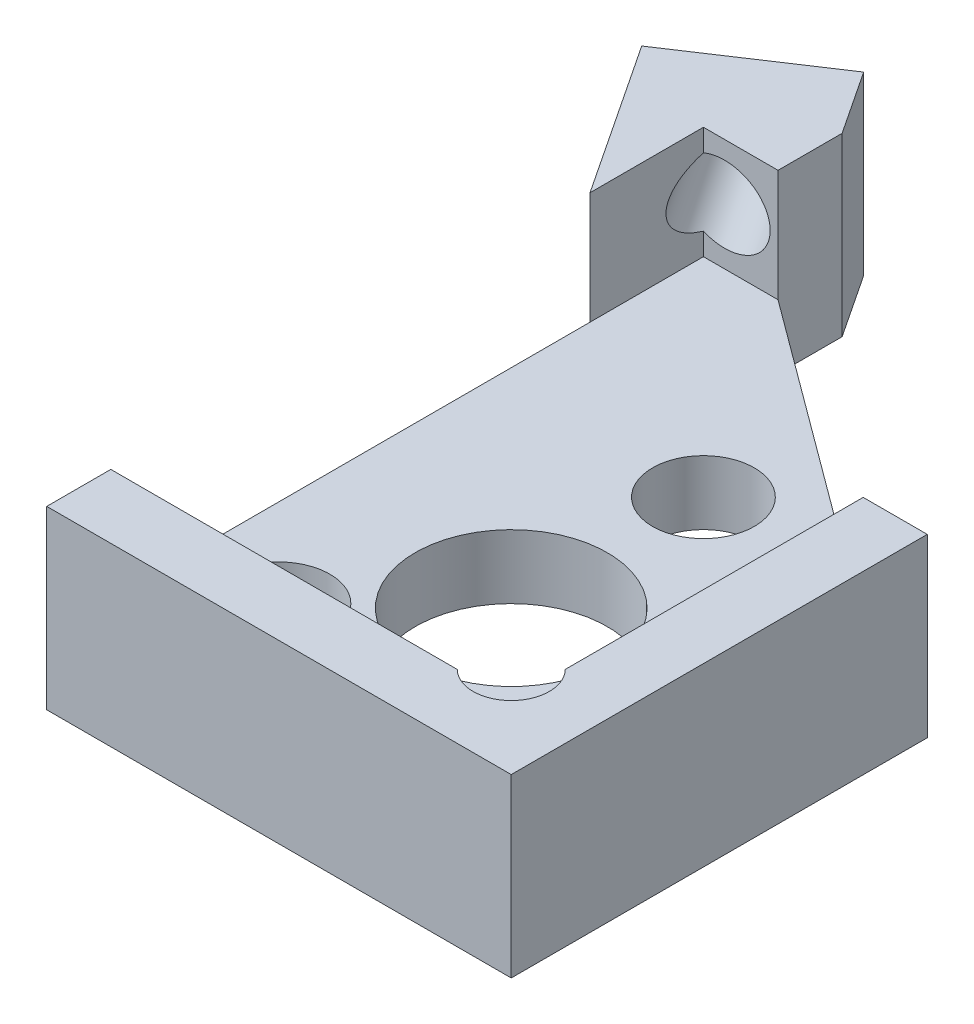
SolidWorks part; units mm, degrees
ref_plane "Front Plane" through (0, 0, 0) normal (0, 0, 1) x (1, 0, 0)
ref_plane "Top Plane" through (0, 0, 0) normal (0, 1, 0) x (1, 0, 0)
ref_plane "Right Plane" through (0, 0, 0) normal (1, 0, 0) x (0, 0, -1)
sketch "Sketch1" plane through (0, 0, 0) normal (0, 1, 0) x (1, 0, 0)
  line L7 (4.125, 5.625) -> (-4.125, 5.625)
  line L8 (4.125, 5.625) -> (4.125, -5.625)
  line L9 (4.125, -5.625) -> (-4.125, -5.625)
  line L10 (-4.125, 5.625) -> (-4.125, -5.625)
  line L11 (4.125, 5.625) -> (-4.125, -5.625) construction
  line L12 (4.125, -5.625) -> (-4.125, 5.625) construction
  point P0 (0, 0)
  point P6 (0, 0)
  dimension "D1" = 8.25
  dimension "D2" = 11.25
extrude "Boss-Extrude1" add sketch "Sketch1" along normal blind 2.75
sketch "Sketch2" plane through (0, 2.75, 0) normal (0, 1, 0) x (1, 0, 0)
  line L0 (-4.125, 5.625) -> (-4.125, -5.625) construction
  line L1 (3.125, 4.625) -> (-3.125, 4.625)
  line L2 (3.125, 4.625) -> (3.125, -4.625)
  line L3 (3.125, -4.625) -> (-3.125, -4.625)
  line L4 (-3.125, 4.625) -> (-3.125, -4.625)
  line L5 (3.125, 4.625) -> (-3.125, -4.625) construction
  line L6 (3.125, -4.625) -> (-3.125, 4.625) construction
  line L7 (4.125, 5.625) -> (-4.125, 5.625) construction
  point P0 (0, 0)
  dimension "D1" = 1
  dimension "D2" = 1
extrude "Cut-Extrude1" cut sketch "Sketch2" against normal offset from surface (1.75 mm away) 1 up to face at (0, 0, 0)
sketch "Sketch3" plane through (0, 1, 0) normal (0, 1, 0) x (1, 0, 0)
  line L0 (-3.125, -4.625) -> (3.125, -4.625) construction
  line L1 (3.125, -4.625) -> (3.125, 4.625) construction
  circle A0 centre (0.125, -1.625) radius 1.5
  dimension "D1" = 3
  dimension "D2" = 3
  dimension "D3" = 3
extrude "Cut-Extrude2" cut sketch "Sketch3" against normal through all
sketch "Sketch6" plane through (0, 2.75, 0) normal (0, 1, 0) x (1, 0, 0)
  line L0 (3.125, -4.625) -> (3.125, 4.625) construction
  line L2 (-3.125, -4.625) -> (3.125, -4.625) construction
  line L3 (3.125, -4.2041) -> (2.7041, -4.2041) construction
  line L4 (2.7041, -4.2041) -> (2.7041, -4.625) construction
  circle A3 centre (2.7041, -4.2041) radius 0.5953
  dimension "D1" = 1.1906
extrude "Cut-Extrude5" cut sketch "Sketch6" against normal up to surface (1.75 mm away) up to face at (0.125, 1, 3.125)
sketch "Sketch7" plane through (0, 1, 0) normal (0, 1, 0) x (1, 0, 0)
  line L0 (2, 1.375) -> (-1.75, 1.375) construction
  line L1 (-1.75, 1.375) -> (-1.75, -3.375) construction
  line L2 (-1.75, -3.375) -> (2, -3.375) construction
  line L3 (2, -3.375) -> (2, 1.375) construction
  line L4 (0.125, 1.375) -> (0.125, -1.625) construction
  circle A0 centre (0.125, 1.375) radius 0.7938
  circle A2 centre (-1.75, -3.375) radius 0.7938
  circle A3 centre (2, -3.375) radius 0.7938
  circle A4 centre (0.125, -1.625) radius 1.5 construction
  dimension "D1" = 1.5875
  dimension "D2" = 3.75
  dimension "D3" = 3
  dimension "D4" = 1.75
extrude "Cut-Extrude6" cut sketch "Sketch7" against normal through all
sketch "Sketch9" plane through (0, 2.75, 0) normal (0, 1, 0) x (1, 0, 0)
  line L0 (-2.62, 6.6211) -> (-4.7047, 5.2413)
  line L1 (-3.3443, 4.4788) -> (-3.9381, 4.083)
  line L2 (-3.3443, 4.4788) -> (-2.444, 5.079)
  line L3 (-2.62, 6.6211) -> (-1.8566, 5.4678)
  line L4 (3.125, -4.625) -> (-2.875, 4.375) construction
  line L5 (3.125, -4.625) -> (-2.875, -4.625) construction
  line L6 (-3.125, -4.625) -> (2.2831, -4.625) construction
  line L8 (-2.875, -4.625) -> (-2.875, 4.375) construction
  line L9 (-2.875, 4.375) -> (3.125, 4.375) construction
  line L10 (3.125, -3.7831) -> (3.125, 4.625) construction
  line L11 (3.125, 4.375) -> (3.125, -4.625) construction
  line L12 (-2.875, 3.7748) -> (-1.9747, 4.375) construction
  line L13 (-2.875, 3.7748) -> (-3.3443, 4.4788) construction
  line L14 (-2.4248, 4.0749) -> (-2.8942, 4.7789) construction
  line L15 (-1.8566, 5.4678) -> (-2.444, 5.079)
  line L16 (-3.9381, 4.083) -> (-4.7047, 5.2413)
  line L17 (-2.8942, 4.7789) -> (-3.6624, 5.9312) construction
  arc A0 (2.2831, -4.625) -> (3.125, -3.7831) centre (2.7041, -4.2041) ccw construction
  dimension "D1" = 6
  dimension "D2" = 9
  dimension "D3" = 1.082
  dimension "D4" = 2.5
extrude "Boss-Extrude2" add sketch "Sketch9" against normal up to surface (2.75 mm away) up to face at (2, 0, 4.1687)
sketch "Sketch10" plane through (-3.8455, 0, -5.81) normal (-0.5519, 0, -0.8339) x (-0.8339, 0, 0.5519)
  line L0 (-0.2196, 1) -> (-0.2196, 1.875) construction
  line L2 (-0.2196, 1.875) -> (-0.2196, 2.75) construction
  line L3 (-1.4696, 2.75) -> (1.0304, 2.75) construction
  line L4 (-0.2196, 1) -> (-0.2196, 0) construction
  line L5 (-1.4696, 0) -> (1.0304, 0) construction
  dimension "D1" = 1
hole_wizard "Tap Drill for #0-80 Tap1" positions "Sketch12" profile "Sketch11" hole size "#0-80" standard "ANSI Inch"
sketch "Sketch12" plane through (-3.8455, 0, -5.81) normal (-0.5519, 0, -0.8339) x (-0.8339, 0, 0.5519)
  point P0 (-0.2196, 1.875)
sketch "Sketch11" plane through (-3.6624, 1.875, -5.9312) normal (0, 1, 0) x (-0.8339, 0, 0.5519)
  line L0 (0, 0) -> (0, 7.4679)
  line L1 (0, 7.4679) -> (0.5956, 7.11)
  line L2 (0.5956, 7.11) -> (0.5956, 0)
  line L5 (0.5956, 0) -> (0, 0)
  line L10 (0, 7.4679) -> (-0.5956, 7.11) construction
  line L11 (0, -6.35) -> (0, 107.95) construction
  dimension "Hole Dia." = 1.1913
  dimension "Hole Depth" = 7.11
  dimension "Drill Angle" = 118
sketch "Sketch13" plane through (0, 2.75, 0) normal (0, 1, 0) x (1, 0, 0)
  line L0 (-1.9607, 5.625) -> (-1.9607, 4.625)
  line L2 (-1.75, -3.375) -> (-3.125, -3.375) construction
  line L3 (3.125, 0.8685) -> (4.125, 0.8685)
  line L4 (4.125, -5.625) -> (4.125, 5.625) construction
  line L5 (4.125, 0.8685) -> (4.125, 5.625)
  line L6 (4.125, 5.625) -> (-1.9607, 5.625)
  line L7 (-4.125, 4.3654) -> (-3.125, 2.8545)
  line L8 (-3.125, 4.625) -> (-3.125, -4.625) construction
  line L9 (-4.125, 4.3654) -> (-4.125, -5.625) construction
  line L10 (-3.125, 2.8545) -> (-3.125, -5.625)
  line L11 (-4.125, -5.625) -> (4.125, -5.625) construction
  line L12 (-3.125, -5.625) -> (-4.125, -5.625)
  line L13 (-4.125, -5.625) -> (-4.125, 4.3654)
  line L15 (-4.7047, 5.2413) -> (-4.125, 4.3654) construction
  line L17 (-1.9607, 4.625) -> (3.125, 0.8685)
  line L18 (3.125, -3.7831) -> (3.125, 4.625) construction
  line L20 (0.125, 1.375) -> (0.9419, 2.481) construction
  line L23 (3.125, 4.625) -> (-3.125, 4.625) construction
extrude "Cut-Extrude7" cut sketch "Sketch13" against normal up to next
